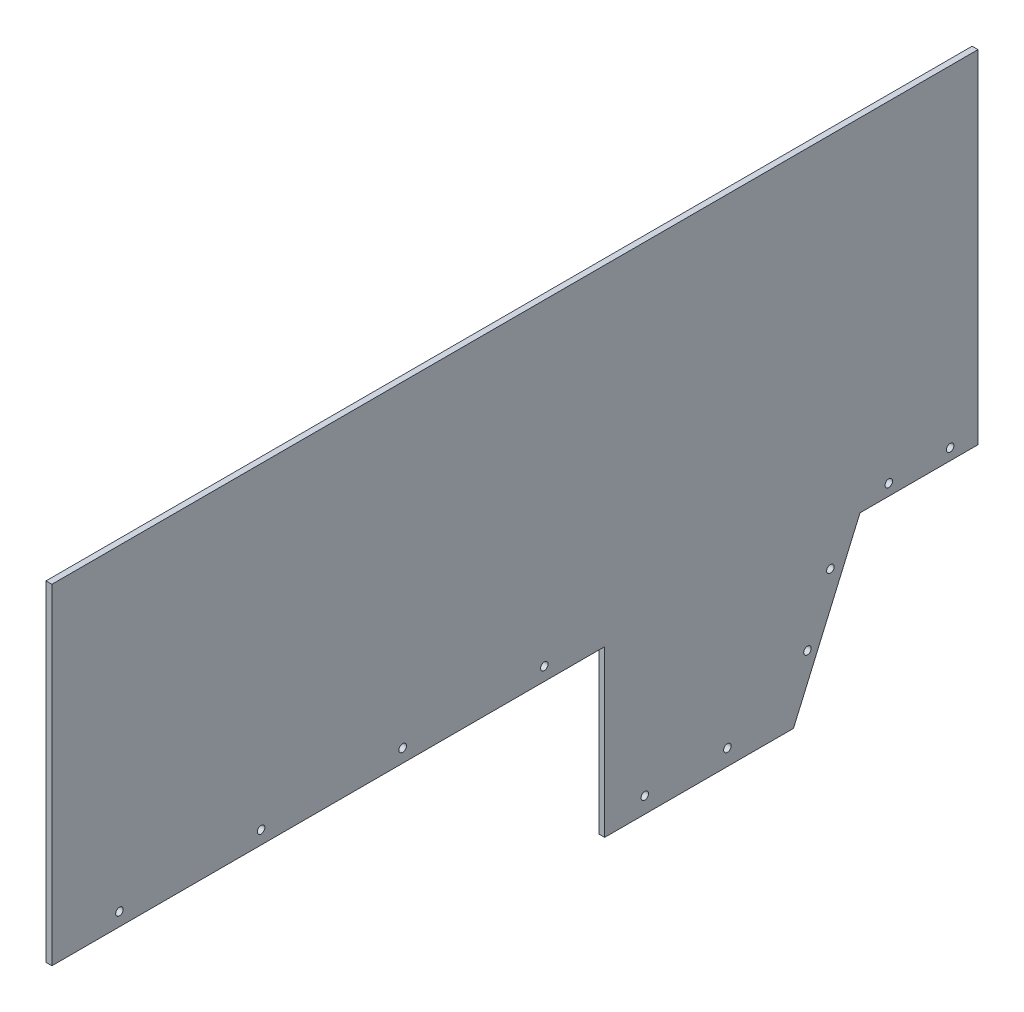
SolidWorks part; units mm, degrees
material "6061-T6 (SS)"
ref_plane "X-Y Datum" through (0, 0, 0) normal (0, 0, 1) x (1, 0, 0)
ref_plane "X-Z Datum" through (0, 0, 0) normal (0, 1, 0) x (1, 0, 0)
ref_plane "Y-Z Datum" through (0, 0, 0) normal (1, 0, 0) x (0, 0, -1)
sketch "Sketch1" plane through (0, 0, 0) normal (1, 0, 0) x (0, 0, -1)
  line L1 (-249.174, 88.9) -> (249.174, 88.9)
  line L2 (-249.174, 88.9) -> (-249.174, -88.9)
  line L3 (-249.174, -88.9) -> (249.174, -88.9)
  line L4 (249.174, 88.9) -> (249.174, -88.9)
  line L5 (-249.174, 88.9) -> (249.174, -88.9) construction
  line L6 (-249.174, -88.9) -> (249.174, 88.9) construction
  point P0 (0, 0)
  dimension "D1" = 177.8
  dimension "D2" = 498.348
extrude "Boss-Extrude1" add sketch "Sketch1" along normal mid plane 3.175
sketch "Sketch2" plane through (1.5875, 0, 0) normal (1, 0, 0) x (0, 0, -1)
  line L0 (249.174, -88.9) -> (249.174, -95.25)
  line L1 (249.174, -95.25) -> (185.674, -95.25)
  line L2 (185.674, -95.25) -> (149.8854, -177.8)
  line L3 (149.8854, -177.8) -> (48.2854, -177.8)
  line L4 (48.2854, -177.8) -> (48.2854, -88.9)
  line L5 (-249.174, -88.9) -> (249.174, -88.9) construction
  line L6 (48.2854, -88.9) -> (249.174, -88.9)
  line L8 (48.2854, -76.2) -> (48.2854, 88.9)
  line L10 (249.174, -88.9) -> (249.174, 88.9) construction
  line M10 (-249.174, -88.9) -> (249.174, -88.9)
  dimension "D1" = 6.35
  dimension "D2" = 63.5
  dimension "D3" = 88.9
  dimension "D4" = 101.6
extrude "Boss-Extrude2" add sketch "Sketch2" against normal blind 3.175 contours L4 L3 L2 L1 L0 M10 region at (1.5875, -129.6106, -113.0883)
sketch "Sketch3" plane through (1.5875, 0, 0) normal (1, 0, 0) x (0, 0, -1)
  line L0 (48.2854, -81.7704) -> (48.2854, -88.9)
  line L2 (48.2854, -81.7704) -> (15.7854, -81.7704)
  circle A1 centre (15.7854, -81.7704) radius 2.025
extrude "Cut-Extrude1" cut sketch "Sketch3" against normal through all contours A1 region at (1.5875, -81.7704, -13.8177)
pattern_linear "LPattern1" count 4 spacing 76.2 along (0, 0, 1) of "Cut-Extrude1"
sketch "Sketch4" plane through (-1.5875, 0, 0) normal (-1, 0, 0) x (0, 0, 1)
  line L0 (-69.8754, -177.8) -> (-69.8754, -169.164)
  line L2 (-149.8854, -177.8) -> (-48.2854, -177.8) construction
  line L3 (-48.2854, -169.164) -> (-69.8754, -169.164)
  line L4 (-48.2854, -177.8) -> (-48.2854, -88.9) construction
  circle A0 centre (-69.8754, -169.164) radius 2.025
extrude "Cut-Extrude2" cut sketch "Sketch4" against normal through all contours L3 A0 L0 | L0 A0 L3 region at (-1.5875, -168.8775, -70.1619) region at (-1.5875, -170.0234, -69.016)
pattern_linear "LPattern2" count 2 spacing 44.45 along (0, 0, -1) of "Cut-Extrude2"
sketch "Sketch5" plane through (-1.5875, 0, 0) normal (-1, 0, 0) x (0, 0, 1)
  line L0 (-162.9577, -147.6475) -> (-157.4113, -145.2429)
  line L1 (-185.674, -95.25) -> (-149.8854, -177.8) construction
  circle A0 centre (-157.4113, -145.2429) radius 2.025
extrude "Cut-Extrude3" cut sketch "Sketch5" against normal through all contours A0 region at (-1.5875, -147.1696, -157.0116)
sketch "Sketch8" plane through (-1.5875, 0, 0) normal (-1, 0, 0) x (0, 0, 1)
  line L2 (-157.4113, -145.2429) -> (-161.6752, -150.6055)
  line L3 (-185.674, -95.25) -> (-149.8854, -177.8) construction
  line L4 (-157.4113, -145.2429) -> (-170.7829, -113.7847)
  line L5 (-169.748, -113.3448) -> (-170.7829, -113.7847)
  circle A0 centre (-169.748, -113.3448) radius 2.025
extrude "Cut-Extrude5" cut sketch "Sketch8" against normal through all contours A0 region at (-1.5875, -114.8599, -168.4925)
sketch "Sketch9" plane through (-1.5875, 0, 0) normal (-1, 0, 0) x (0, 0, 1)
  line L0 (-201.1707, -95.25) -> (-201.1707, -89.154)
  line L1 (-249.174, -95.25) -> (-185.674, -95.25) construction
  circle A0 centre (-201.1707, -89.154) radius 2.025
extrude "Cut-Extrude6" cut sketch "Sketch9" against normal through all contours A0 region at (-1.5875, -90.5454, -199.7793)
pattern_linear "LPattern4" count 2 spacing 33.02 along (0, 0, -1) of "Cut-Extrude6"
